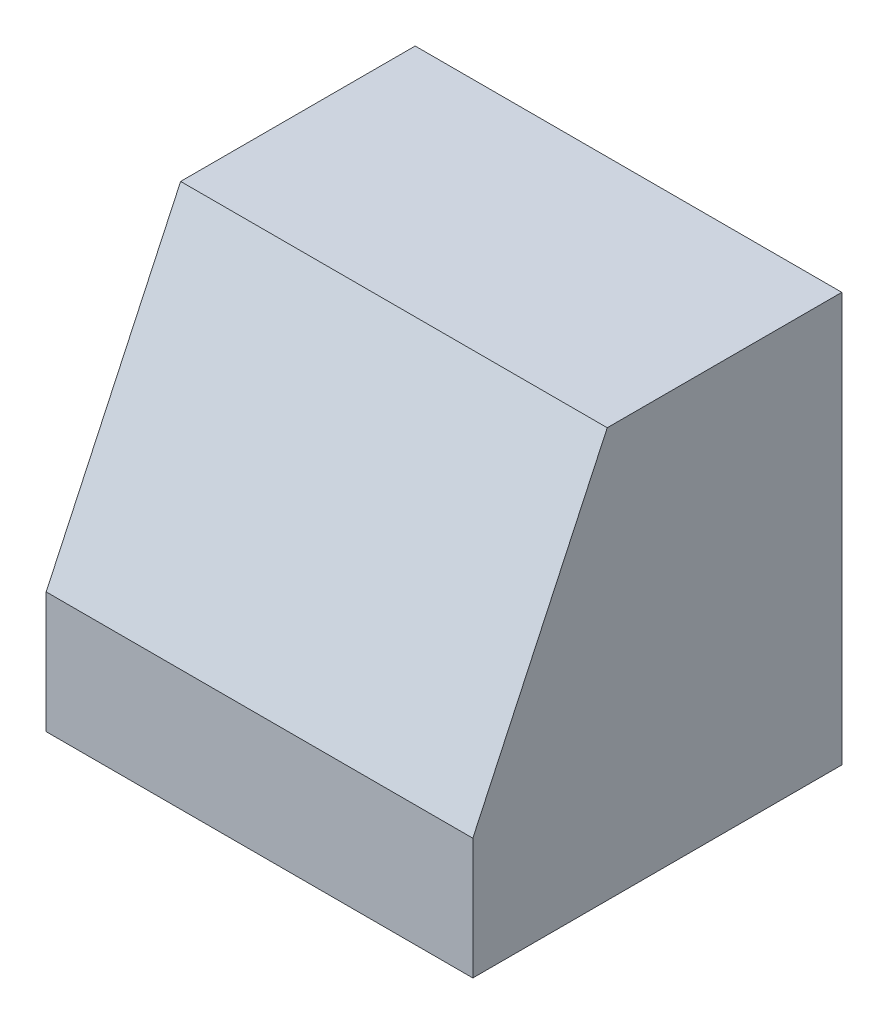
SolidWorks part; units mm, degrees
material "NBR"
ref_plane "Спереди" through (0, 0, 0) normal (0, 0, 1) x (1, 0, 0)
ref_plane "Сверху" through (0, 0, 0) normal (0, 1, 0) x (1, 0, 0)
ref_plane "Справа" through (0, 0, 0) normal (1, 0, 0) x (0, 0, -1)
sketch "Эскиз1" plane through (0, 0, 0) normal (0, 0, 1) x (1, 0, 0)
  line L1 (-6.6453, 0.8695) -> (0.7547, 0.8695)
  line L2 (-6.6453, 0.8695) -> (-6.6453, -6.2305)
  line L3 (-6.6453, -6.2305) -> (0.7547, -6.2305)
  line L4 (0.7547, 0.8695) -> (0.7547, -6.2305)
  circle A0 centre (-2.9453, -2.3805) radius 1.75
  dimension "D3" = 3.5
  dimension "D1" = 7.4
  dimension "D2" = 7.1
  dimension "D4" = 3.25
extrude "Бобышка-Вытянуть1" add sketch "Эскиз1" along normal blind 6.4 contours L4 L1 L2 L3 A0 | A0 region at (-2.9453, 0.767, 0) region at (-2.9453, -2.3805, 0)
extrude "Бобышка-Вытянуть2" add sketch "Эскиз1<3>" against normal blind 1.3 contours A0
sketch "Эскиз1<3>" plane through (0, 0, 0) normal (0, 0, 1) x (1, 0, 0) same geometry as "Эскиз1"
chamfer "Фаска1" distance 5 angle 25 1 edges at (-2.9453, 0.8695, 6.4) first distance on face at (-2.9453, -2.6805, 6.4)
